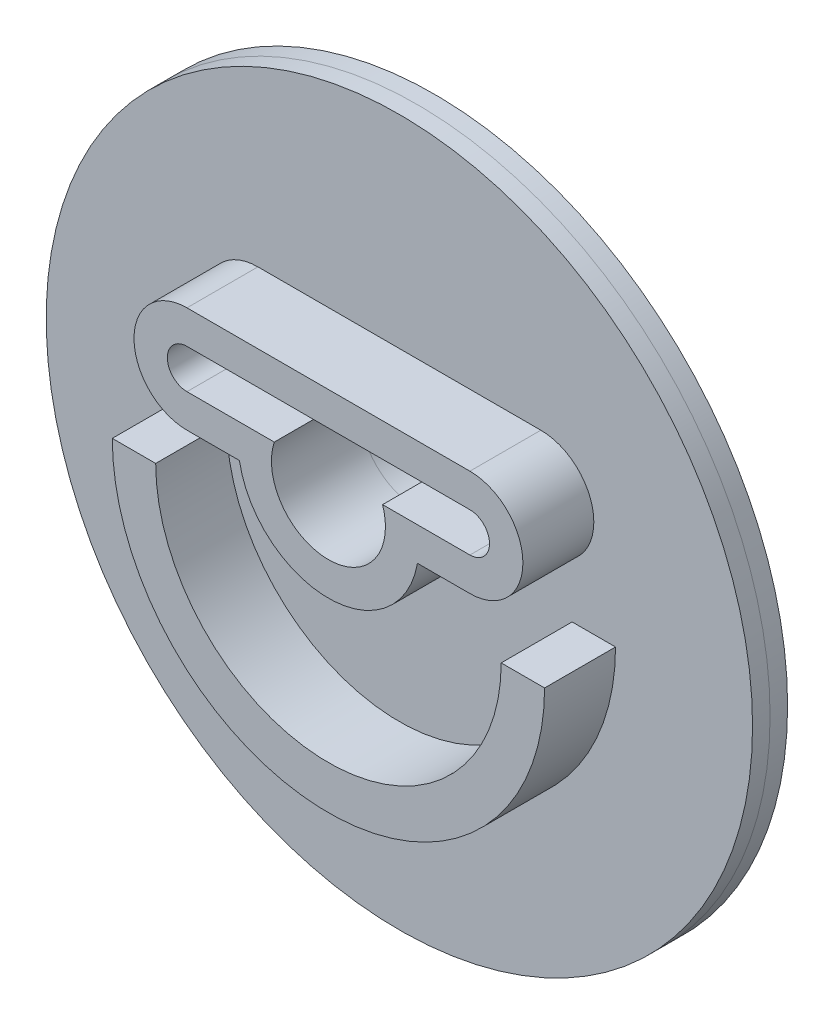
SolidWorks part; units mm, degrees
ref_plane "Front Plane" through (0, 0, 0) normal (0, 0, 1) x (1, 0, 0)
ref_plane "Top Plane" through (0, 0, 0) normal (0, 1, 0) x (1, 0, 0)
ref_plane "Right Plane" through (0, 0, 0) normal (1, 0, 0) x (0, 0, -1)
sketch "Sketch1" plane through (0, 0, 0) normal (0, 0, 1) x (1, 0, 0)
  line L0 (0, 29.8051) -> (0, -31.034) construction
  line L1 (0, 21.16) -> (30.3616, 21.16) construction
  line L2 (0, 10.425) -> (27.4702, 10.425) construction
  line L7 (0, 7.983) -> (0, -1.8885) construction
  circle A0 centre (0, 0) radius 21.16
  point P10 (-7.5124, 8.4374)
  point P12 (9.4132, 9.0185)
  point P13 (7.5124, 8.4374)
  point P25 (-3.5248, 8.4374)
  point P28 (-7.5124, 8.4374)
  point P29 (11.5, 8.4374)
  point P31 (-5.6117, 9.0185)
  point P32 (7.5124, 8.4374)
  dimension "D3" = 42.32
extrude "Boss-Extrude2" add sketch "Sketch1" along normal blind 2.1
sketch "Sketch3" plane through (0, 0, 2.1) normal (0, 0, 1) x (1, 0, 0)
  line L0 (0, 23.901) -> (0, 17.4278) construction
  line L1 (0, 21.16) -> (22.4833, 21.16) construction
  line L2 (0, 7.01) -> (23.6909, 7.01) construction
  circle A1 centre (0, 3.595) radius 3.415
  circle A2 centre (0, 0) radius 21.16 construction
  dimension "D1" = 6.83
  dimension "D2" = 14.15
extrude "Cut-Extrude1" cut sketch "Sketch3" against normal through all and the other way through all
sketch "Sketch4" plane through (0, 0, 2.1) normal (0, 0, 1) x (1, 0, 0)
  line L0 (0, 23.1767) -> (0, -22.0392) construction
  line L1 (-9.65, 5.835) -> (-9.65, 17.6951) construction
  line L2 (9.65, 5.835) -> (9.65, 17.3084) construction
  line L3 (0, 7.01) -> (-12.9667, 7.01) construction
  line L4 (-8.475, 7.01) -> (8.475, 7.01)
  line L5 (-8.475, 4.66) -> (-3.2447, 4.66)
  line L6 (-8.475, 9.01) -> (8.475, 9.01)
  line L7 (-8.475, 2.66) -> (-5.3337, 2.66)
  line L8 (3.2447, 4.66) -> (8.475, 4.66)
  line L9 (5.3337, 2.66) -> (8.475, 2.66)
  line L10 (-11.65, 5.835) -> (-11.65, 13.4132) construction
  line L11 (11.65, 5.835) -> (11.65, 12.3871) construction
  arc A0 (-8.475, 7.01) -> (-8.475, 4.66) centre (-8.475, 5.835) ccw
  arc A1 (8.475, 4.66) -> (8.475, 7.01) centre (8.475, 5.835) ccw
  circle A3 centre (0, 3.595) radius 3.415 construction
  arc A5 (8.475, 2.66) -> (8.475, 9.01) centre (8.475, 5.835) ccw
  arc A7 (-8.475, 9.01) -> (-8.475, 2.66) centre (-8.475, 5.835) ccw
  circle A8 centre (0, 3.595) radius 5.415
  arc A9 (-5.3337, 2.66) -> (5.3337, 2.66) centre (0, 3.595) ccw
  circle A11 centre (8.475, 5.835) radius 3.175 construction
  circle A12 centre (8.475, 5.835) radius 1.175 construction
  circle A14 centre (0, 3.595) radius 3.415
  arc A15 (-3.2447, 4.66) -> (3.2447, 4.66) centre (0, 3.595) ccw
  point P4 (11.65, 5.835)
  point P6 (-5.3, 5.835)
  point P22 (9.5987, 6.1785)
  point P27 (-7.3513, 6.1785)
  dimension "D2" = 2.35
  dimension "D1" = 19.3
  dimension "D6" = 23.3
  dimension "D3" = 2
  dimension "D4" = 2
  dimension "D5" = 0
extrude "Boss-Extrude3" add sketch "Sketch4" along normal blind 4.25
sketch "Sketch5" plane through (0, 0, 2.1) normal (0, 0, 1) x (1, 0, 0)
  line L0 (10.35, 0) -> (12.95, 0)
  line L1 (-10.35, 0) -> (-12.95, 0)
  arc A0 (-10.35, 0) -> (10.35, 0) centre (0, 0) ccw
  arc A1 (-12.95, 0) -> (12.95, 0) centre (0, 0) ccw
  circle A3 centre (0, 0) radius 12.95 construction
  circle A4 centre (0, 0) radius 10.35 construction
  point P4 (9.8978, 3.026)
  point P5 (12.95, 0)
  dimension "D1" = 20.7
  dimension "D2" = 2.6
extrude "Boss-Extrude4" add sketch "Sketch5" along normal blind 4.25
sketch "Sketch6" plane through (0, 0, 0) normal (0, 0, -1) x (-1, 0, 0)
  circle A2 centre (0, 3.595) radius 4.85
  circle A6 centre (0, 3.595) radius 3.415
  circle A7 centre (0, 3.595) radius 3.415
  dimension "D2" = 0
  dimension "D1" = 9.7
extrude "Boss-Extrude5" add sketch "Sketch6" along normal blind 1.48
sketch "Sketch7" plane through (0, 0, 0) normal (0, 0, -1) x (-1, 0, 0)
  circle A0 centre (0, 0) radius 10
  circle A1 centre (0, 0) radius 11.25
  dimension "D1" = 20
  dimension "D2" = 22.5
extrude "Boss-Extrude6" add sketch "Sketch7" along normal blind 6
sketch "Sketch8" plane through (0, 0, 0) normal (1, 0, 0) x (0, 0, -1)
  line L0 (-1.05, 21.16) -> (-1.05, -21.16)
  line L1 (0, 21.16) -> (-2.1, 21.16) construction
  line L2 (-2.1, -21.16) -> (0, -21.16) construction
split "Split1" trim tools "Sketch8" bodies to split 109 resulting bodies 110 111
